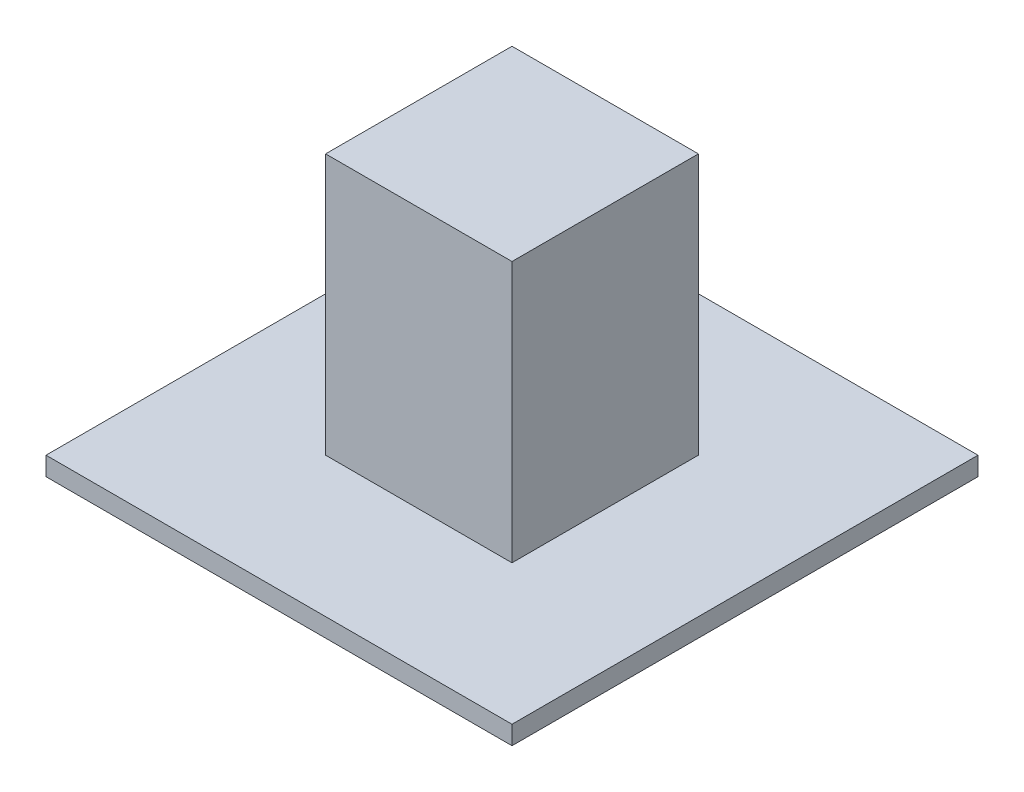
SolidWorks part; units mm, degrees
ref_plane "Front Plane" through (0, 0, 0) normal (0, 0, 1) x (1, 0, 0)
ref_plane "Top Plane" through (0, 0, 0) normal (0, 1, 0) x (1, 0, 0)
ref_plane "Right Plane" through (0, 0, 0) normal (1, 0, 0) x (0, 0, -1)
sketch "Sketch1" plane through (0, 0, 0) normal (0, 1, 0) x (1, 0, 0)
  line L1 (-1, -1) -> (1, -1)
  line L2 (-1, -1) -> (-1, 1)
  line L3 (-1, 1) -> (1, 1)
  line L4 (1, -1) -> (1, 1)
  line L5 (-1, -1) -> (1, 1) construction
  line L6 (-1, 1) -> (1, -1) construction
  point P0 (0, 0)
  dimension "D1" = 2
  dimension "D2" = 2
extrude "Boss-Extrude1" add sketch "Sketch1" along normal blind 2.8
sketch "Sketch2" plane through (0, 0, 0) normal (0, 1, 0) x (1, 0, 0)
  line L1 (-2.5, -2.5) -> (2.5, -2.5)
  line L2 (-2.5, -2.5) -> (-2.5, 2.5)
  line L3 (-2.5, 2.5) -> (2.5, 2.5)
  line L4 (2.5, -2.5) -> (2.5, 2.5)
  line L5 (-2.5, -2.5) -> (2.5, 2.5) construction
  line L6 (-2.5, 2.5) -> (2.5, -2.5) construction
  point P0 (0, 0)
  dimension "D1" = 5
  dimension "D2" = 5
extrude "Boss-Extrude2" add sketch "Sketch2" against normal blind 0.2
sketch "Sketch3" plane through (0, -0.2, 0) normal (0, -1, 0) x (-1, 0, 0)
  circle A0 centre (-0.6428, 0.9803) radius 0.5
  point P2 (-1.0822, 1)
  point P3 (0, 0)
  dimension "D1" = 1
extrude "Boss-Extrude3" add sketch "Sketch3" along normal blind 1
